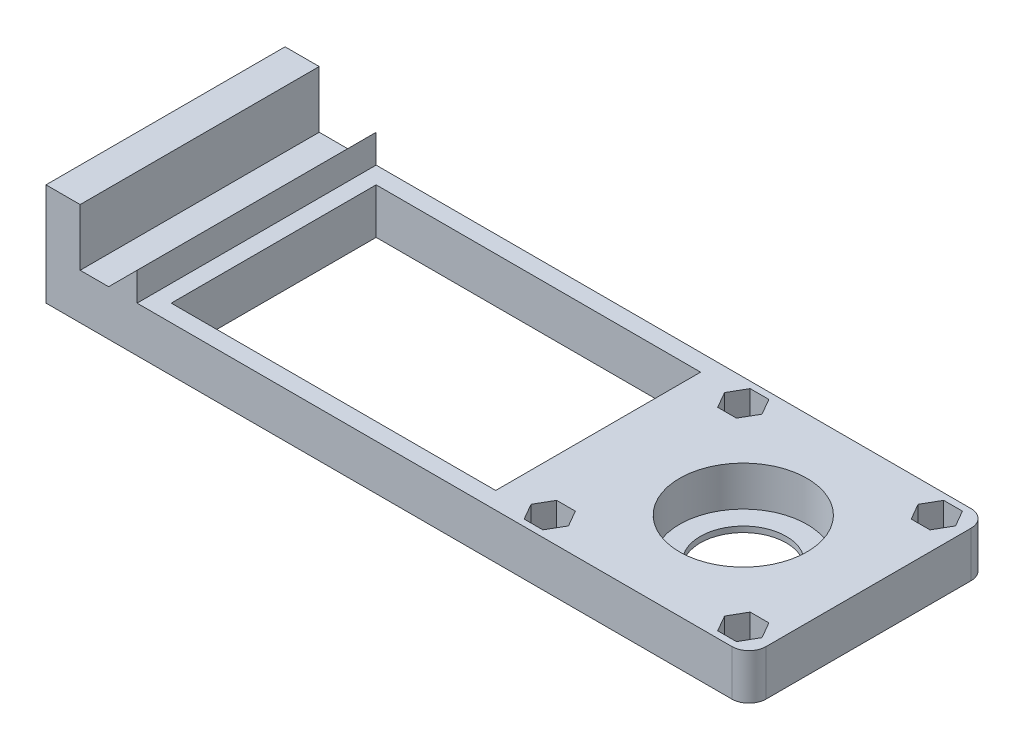
SolidWorks part; units mm, degrees
ref_plane "Front Plane" through (0, 0, 0) normal (0, 0, 1) x (1, 0, 0)
ref_plane "Top Plane" through (0, 0, 0) normal (0, 1, 0) x (1, 0, 0)
ref_plane "Right Plane" through (0, 0, 0) normal (1, 0, 0) x (0, 0, -1)
sketch "Sketch1" plane through (0, 0, 0) normal (0, 1, 0) x (1, 0, 0)
  line L1 (-61.75, -21) -> (61.75, -21)
  line L2 (-61.75, -21) -> (-61.75, 21)
  line L3 (-61.75, 21) -> (61.75, 21)
  line L4 (61.75, -21) -> (61.75, 21)
  line L5 (-61.75, -21) -> (61.75, 21) construction
  line L6 (-61.75, 21) -> (61.75, -21) construction
  point P0 (0, 0)
  dimension "D1" = 123.5
  dimension "D2" = 42
extrude "Boss-Extrude1" add sketch "Sketch1" along normal blind 8
sketch "Sketch2" plane through (0, 8, 0) normal (0, 1, 0) x (1, 0, 0)
  line L0 (61.75, 0) -> (39.75, 0) construction
  line L1 (61.75, -21) -> (61.75, 21) construction
  circle A0 centre (39.75, 0) radius 11.2
  dimension "D2" = 22.4
  dimension "D1" = 22
extrude "Cut-Extrude1" cut sketch "Sketch2" against normal blind 7
sketch "Sketch3" plane through (0, 0, 0) normal (0, -1, 0) x (1, 0, 0)
  line L0 (61.75, 0) -> (39.75, 0) construction
  line L1 (61.75, 21) -> (61.75, -21) construction
  circle A0 centre (39.75, 0) radius 7.55
  dimension "D2" = 15.1
  dimension "D1" = 22
extrude "Cut-Extrude2" cut sketch "Sketch3" against normal up to next
sketch "Sketch9" plane through (0, 8, 0) normal (0, 1, 0) x (1, 0, 0)
  line L0 (56.75, 21) -> (56.75, 17) construction
  line L1 (61.75, 21) -> (-61.75, 21) construction
  line L2 (56.75, 17) -> (61.75, 17) construction
  line L3 (61.75, -21) -> (61.75, 21) construction
  line L4 (61.75, 0) -> (39.75, 0) construction
  line L5 (39.75, 0) -> (39.75, 21) construction
  line L6 (61.75, 21) -> (-61.75, 21) construction
  line L7 (58.3954, 19.85) -> (55.1046, 19.85)
  line L8 (55.1046, 19.85) -> (53.4591, 17)
  line L9 (53.4591, 17) -> (55.1046, 14.15)
  line L10 (55.1046, 14.15) -> (58.3954, 14.15)
  line L11 (58.3954, 14.15) -> (60.0409, 17)
  line L12 (60.0409, 17) -> (58.3954, 19.85)
  line L13 (60.0409, -17) -> (58.3954, -19.85)
  line L14 (58.3954, -19.85) -> (55.1046, -19.85)
  line L15 (55.1046, -19.85) -> (53.4591, -17)
  line L16 (53.4591, -17) -> (55.1046, -14.15)
  line L17 (55.1046, -14.15) -> (58.3954, -14.15)
  line L18 (58.3954, -14.15) -> (60.0409, -17)
  line L19 (19.4591, 17) -> (21.1046, 19.85)
  line L20 (21.1046, 19.85) -> (24.3954, 19.85)
  line L21 (24.3954, 19.85) -> (26.0409, 17)
  line L22 (26.0409, 17) -> (24.3954, 14.15)
  line L23 (24.3954, 14.15) -> (21.1046, 14.15)
  line L24 (21.1046, 14.15) -> (19.4591, 17)
  line L25 (21.1046, -14.15) -> (19.4591, -17)
  line L26 (24.3954, -14.15) -> (21.1046, -14.15)
  line L27 (26.0409, -17) -> (24.3954, -14.15)
  line L28 (24.3954, -19.85) -> (26.0409, -17)
  line L29 (21.1046, -19.85) -> (24.3954, -19.85)
  line L30 (19.4591, -17) -> (21.1046, -19.85)
  circle A7 centre (56.75, 17) radius 2.85 construction
  point P4 (59.2182, 15.575)
  dimension "D3" = 5.7
  dimension "D1" = 4
  dimension "D2" = 5
  dimension "D4" = 0
extrude "Cut-Extrude4" cut sketch "Sketch9" against normal blind 6
sketch "Sketch10" plane through (0, 0, 0) normal (0, -1, 0) x (1, 0, 0)
  line L0 (56.75, 21) -> (56.75, 17) construction
  line L1 (-61.75, 21) -> (61.75, 21) construction
  line L2 (56.75, 17) -> (61.75, 17) construction
  line L3 (61.75, 21) -> (61.75, -21) construction
  line L4 (39.75, 0) -> (39.75, 21) construction
  line L23 (39.75, 0) -> (61.75, 0) construction
  circle A1 centre (56.75, 17) radius 1.75
  circle A3 centre (22.75, 17) radius 1.75
  circle A4 centre (56.75, -17) radius 1.75
  circle A5 centre (22.75, -17) radius 1.75
  dimension "D3" = 3.5
  dimension "D1" = 4
  dimension "D2" = 5
extrude "Cut-Extrude5" cut sketch "Sketch10" against normal blind 2
sketch "Sketch12" plane through (0, 0, -21) normal (0, 0, -1) x (-1, 0, 0)
  line L0 (55.75, 8) -> (50.75, 8) construction
  line L1 (61.75, 8) -> (55.75, 8)
  line L2 (61.75, 8) -> (61.75, 18)
  line L3 (61.75, 18) -> (55.75, 18)
  line L4 (55.75, 8) -> (55.75, 18)
  line L5 (-61.75, 8) -> (61.75, 8) construction
  line L6 (50.75, 8) -> (45.75, 8)
  line L7 (45.75, 8) -> (45.75, 13)
  line L8 (45.75, 13) -> (50.75, 8)
  dimension "D1" = 10
  dimension "D2" = 6
  dimension "D3" = 5
  dimension "D4" = 5
  dimension "D5" = 5
extrude "Boss-Extrude2" add sketch "Sketch12" against normal up to surface (42 mm away) up to face at (0, 4, 21)
fillet "Fillet1" radius 3 2 edges at (61.75, 4, -21) (61.75, 4, 21)
sketch "Sketch13" plane through (0, 8, 0) normal (0, 1, 0) x (1, 0, 0)
  line L0 (-42.75, 21) -> (-42.75, 18) construction
  line L1 (58.75, 21) -> (-45.75, 21) construction
  line L2 (-42.75, 18) -> (-45.75, 18) construction
  line L3 (-45.75, -21) -> (-45.75, 21) construction
  line L5 (-42.75, 18) -> (14.25, 18)
  line L6 (-42.75, 18) -> (-42.75, -18)
  line L7 (-42.75, -18) -> (14.25, -18)
  line L8 (14.25, 18) -> (14.25, -18)
  dimension "D1" = 3
  dimension "D2" = 3
  dimension "D3" = 36
  dimension "D4" = 57
extrude "Cut-Extrude6" cut sketch "Sketch13" against normal through all
